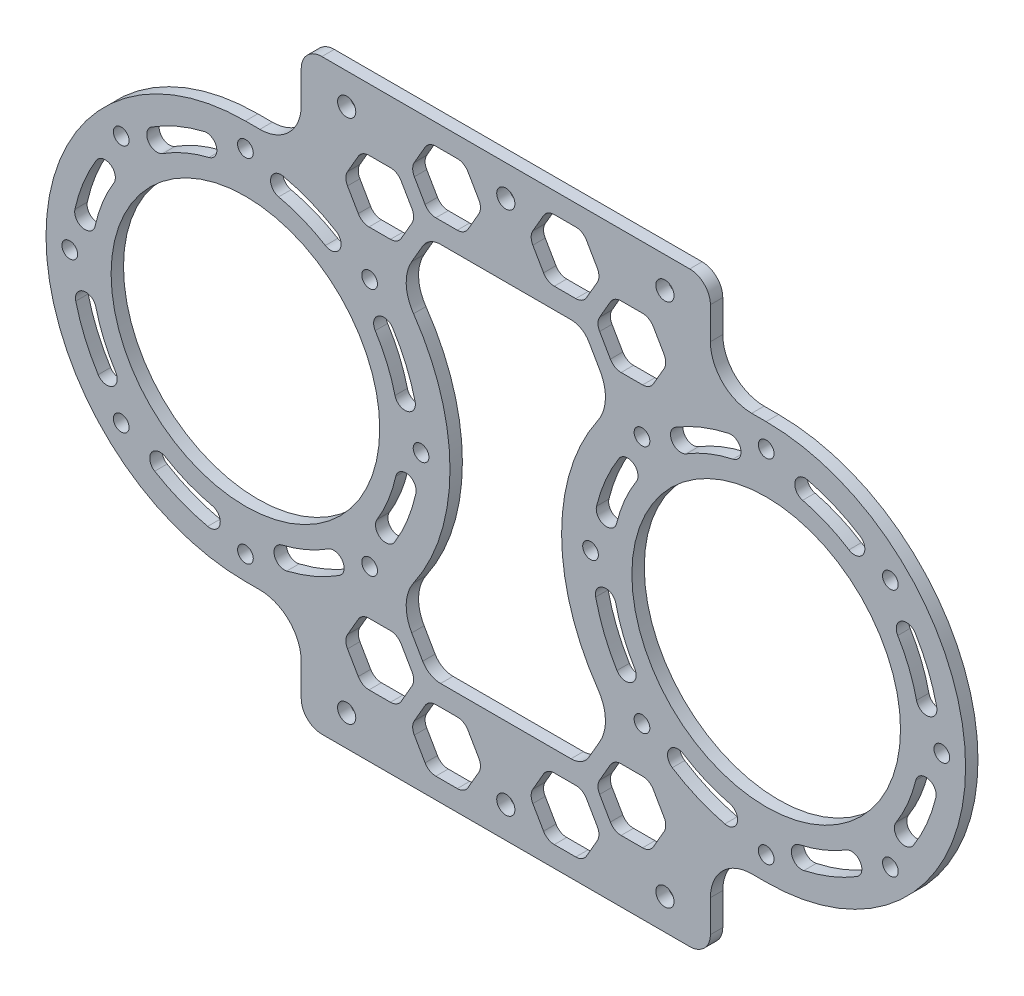
SolidWorks part; units mm, degrees
ref_plane "前视基准面" through (0, 0, 0) normal (0, 0, 1) x (1, 0, 0)
ref_plane "上视基准面" through (0, 0, 0) normal (0, 1, 0) x (1, 0, 0)
ref_plane "右视基准面" through (0, 0, 0) normal (1, 0, 0) x (0, 0, -1)
other "Configuration Table"
sketch "草图1" plane through (0, 0, 0) normal (0, 0, 1) x (1, 0, 0)
  line L0 (0, 0) -> (126, 0) construction
  line L1 (0, 48.25) -> (126, 48.25)
  line L2 (0, -48.25) -> (126, -48.25)
  line L3 (63, 48.25) -> (63, -48.25) construction
  arc A0 (0, 48.25) -> (0, -48.25) centre (0, 0) ccw
  arc A1 (126, -48.25) -> (126, 48.25) centre (126, 0) ccw
  circle A2 centre (126, 0) radius 32.5
  circle A3 centre (0, 0) radius 32.5
  circle A4 centre (0, 0) radius 42.5 construction
  circle A5 centre (126, 0) radius 42.5 construction
  circle A6 centre (0, 42.5) radius 1.9
  circle A7 centre (30.052, 30.052) radius 1.9
  circle A8 centre (42.5, 0) radius 1.9
  circle A9 centre (30.052, -30.052) radius 1.9
  circle A10 centre (0, -42.5) radius 1.9
  circle A11 centre (-30.052, -30.052) radius 1.9
  circle A12 centre (-42.5, 0) radius 1.9
  circle A13 centre (-30.052, 30.052) radius 1.9
  circle A14 centre (156.052, 30.052) radius 1.9
  circle A15 centre (83.5, 0) radius 1.9
  circle A16 centre (95.948, -30.052) radius 1.9
  circle A17 centre (126, -42.5) radius 1.9
  circle A18 centre (156.052, -30.052) radius 1.9
  circle A19 centre (168.5, 0) radius 1.9
  circle A20 centre (126, 0) radius 42.5 construction
  circle A21 centre (126, 42.5) radius 1.9
  circle A22 centre (95.948, 30.052) radius 1.9
  point P3 (63, 0)
  point P35 (0, 0)
  dimension "D2" = 48.25
  dimension "D3" = 65
  dimension "D4" = 85
  dimension "D5" = 3.8
  dimension "D1" = 126
  dimension "D7" = 45
  dimension "D6" = 8
extrude "凸台-拉伸1" add sketch "草图1" along normal blind 3
sketch "草图2" plane through (0, 0, 3) normal (0, 0, 1) x (1, 0, 0)
  line L0 (63, 48.25) -> (63, -48.25) construction
  line L1 (13.5, 48.25) -> (112.5, 48.25)
  line L2 (0, -48.25) -> (126, -48.25)
  line L3 (126, 48.25) -> (0, 48.25)
  line L4 (0, -48.25) -> (126, -48.25)
  line L5 (126, 48.25) -> (0, 48.25)
  line L6 (13.5, 48.25) -> (13.5, 76)
  line L7 (13.5, 76) -> (112.5, 76)
  line L8 (112.5, 76) -> (112.5, 48.25)
  line L9 (-48.25, 0) -> (174.25, 0) construction
  line L10 (13.5, -76) -> (112.5, -76)
  line L11 (13.5, -48.25) -> (13.5, -76)
  line L12 (13.5, -48.25) -> (112.5, -48.25)
  line L13 (112.5, -76) -> (112.5, -48.25)
  arc A2 (0, 48.25) -> (0, -48.25) centre (0, 0) ccw
  arc A3 (126, -48.25) -> (126, 48.25) centre (126, 0) ccw
  arc A4 (0, 48.25) -> (0, -48.25) centre (0, 0) ccw
  arc A5 (126, -48.25) -> (126, 48.25) centre (126, 0) ccw
  line M19 (126, 48.25) -> (0, 48.25)
  dimension "D2" = 99
  dimension "D3" = 27.75
  dimension "D1" = 0
extrude "凸台-拉伸2" add sketch "草图2" against normal blind 3 contours L8 L7 L6 L5 M19 | L10 L13 L12 L11 region at (63, 62.125, 3)
sketch "草图3" plane through (0, 0, 3) normal (0, 0, 1) x (1, 0, 0)
  line L0 (13.5, 63.5) -> (112.5, 63.5) construction
  line L1 (13.5, 48.25) -> (13.5, 76) construction
  line L2 (112.5, 76) -> (112.5, 48.25) construction
  line L3 (13.5, 76) -> (112.5, 76) construction
  line L4 (63, 76) -> (63, -76) construction
  line L5 (13.5, -76) -> (112.5, -76) construction
  line L6 (-48.25, 0) -> (174.25, 0) construction
  arc A0 (0, 48.25) -> (0, -48.25) centre (0, 0) ccw construction
  arc A1 (126, -48.25) -> (126, 48.25) centre (126, 0) ccw construction
  circle A2 centre (63, 63.5) radius 2.2
  circle A3 centre (24.5, 63.5) radius 2.2
  circle A4 centre (101.5, 63.5) radius 2.2
  circle A5 centre (101.5, -63.5) radius 2.2
  circle A6 centre (63, -63.5) radius 2.2
  circle A7 centre (24.5, -63.5) radius 2.2
  dimension "D2" = 77
  dimension "D3" = 4.4
  dimension "D1" = 12.5
extrude "切除-拉伸1" cut sketch "草图3" against normal blind 55
sketch "草图5" plane through (0, 0, 3) normal (0, 0, 1) x (1, 0, 0)
  line L0 (-48.25, 0) -> (174.25, 0) construction
  line L2 (37.6962, 42.5) -> (40.2942, 47)
  line L3 (40.2942, 50) -> (37.6962, 54.5)
  line L4 (35.0981, 56) -> (29.9019, 56)
  line L5 (63, 76) -> (63, -76) construction
  line L6 (13.5, -76) -> (112.5, -76)
  line L7 (112.5, -76) -> (112.5, -48.25)
  line L8 (112.5, 48.25) -> (112.5, 76)
  line L9 (112.5, 76) -> (13.5, 76)
  line L10 (13.5, 76) -> (13.5, 48.25)
  line L11 (13.5, -48.25) -> (13.5, -76)
  line L12 (13.5, -76) -> (112.5, -76)
  line L13 (112.5, -76) -> (112.5, -48.25)
  line L14 (112.5, 48.25) -> (112.5, 76)
  line L15 (112.5, 76) -> (13.5, 76)
  line L16 (13.5, 76) -> (13.5, 48.25)
  line L17 (13.5, -48.25) -> (13.5, -76)
  line L18 (27.3038, 54.5) -> (24.7058, 50)
  line L19 (24.7058, 47) -> (27.3038, 42.5)
  line L20 (29.9019, 41) -> (35.0981, 41)
  line L22 (54.4393, 33.5) -> (57.0374, 38)
  line L23 (57.0374, 41) -> (54.4393, 45.5)
  line L24 (51.8412, 47) -> (46.6451, 47)
  line L25 (44.047, 45.5) -> (41.4489, 41)
  line L26 (41.4489, 38) -> (44.047, 33.5)
  line L27 (46.6451, 32) -> (51.8412, 32)
  line L28 (57.9034, 39.5) -> (57.9034, 20.5)
  line L35 (53.862, 52.5) -> (56.46, 57)
  line L36 (56.46, 60) -> (53.862, 64.5)
  line L37 (51.2639, 66) -> (46.0677, 66)
  line L38 (43.4697, 64.5) -> (40.8716, 60)
  line L39 (40.8716, 57) -> (43.4697, 52.5)
  line L40 (46.0677, 51) -> (51.2639, 51)
  line L41 (54.4393, 14.5) -> (57.0374, 19)
  line L42 (57.0374, 22) -> (54.4393, 26.5)
  line L43 (51.8412, 28) -> (46.6451, 28)
  line L44 (44.047, 26.5) -> (41.4489, 22)
  line L45 (41.4489, 19) -> (44.047, 14.5)
  line L46 (46.6451, 13) -> (51.8412, 13)
  line L119 (46.0677, -51) -> (51.2639, -51)
  line L120 (40.8716, -57) -> (43.4697, -52.5)
  line L121 (43.4697, -64.5) -> (40.8716, -60)
  line L122 (51.2639, -66) -> (46.0677, -66)
  line L123 (56.46, -60) -> (53.862, -64.5)
  line L124 (53.862, -52.5) -> (56.46, -57)
  line L125 (46.6451, -13) -> (51.8412, -13)
  line L126 (41.4489, -19) -> (44.047, -14.5)
  line L127 (44.047, -26.5) -> (41.4489, -22)
  line L128 (51.8412, -28) -> (46.6451, -28)
  line L129 (57.0374, -22) -> (54.4393, -26.5)
  line L130 (54.4393, -14.5) -> (57.0374, -19)
  line L131 (46.6451, -32) -> (51.8412, -32)
  line L132 (41.4489, -38) -> (44.047, -33.5)
  line L133 (44.047, -45.5) -> (41.4489, -41)
  line L134 (51.8412, -47) -> (46.6451, -47)
  line L135 (57.0374, -41) -> (54.4393, -45.5)
  line L136 (54.4393, -33.5) -> (57.0374, -38)
  line L137 (29.9019, -41) -> (35.0981, -41)
  line L138 (24.7058, -47) -> (27.3038, -42.5)
  line L139 (27.3038, -54.5) -> (24.7058, -50)
  line L140 (35.0981, -56) -> (29.9019, -56)
  line L141 (40.2942, -50) -> (37.6962, -54.5)
  line L142 (37.6962, -42.5) -> (40.2942, -47)
  line L143 (84.5511, -38) -> (81.953, -33.5)
  line L144 (81.953, -45.5) -> (84.5511, -41)
  line L145 (74.1588, -47) -> (79.3549, -47)
  line L146 (68.9626, -41) -> (71.5607, -45.5)
  line L147 (71.5607, -33.5) -> (68.9626, -38)
  line L148 (79.3549, -32) -> (74.1588, -32)
  line L149 (85.1284, -57) -> (82.5303, -52.5)
  line L150 (82.5303, -64.5) -> (85.1284, -60)
  line L151 (74.7361, -66) -> (79.9323, -66)
  line L152 (69.54, -60) -> (72.138, -64.5)
  line L153 (72.138, -52.5) -> (69.54, -57)
  line L154 (79.9323, -51) -> (74.7361, -51)
  line L155 (101.2942, -47) -> (98.6962, -42.5)
  line L156 (98.6962, -54.5) -> (101.2942, -50)
  line L157 (90.9019, -56) -> (96.0981, -56)
  line L158 (85.7058, -50) -> (88.3038, -54.5)
  line L159 (88.3038, -42.5) -> (85.7058, -47)
  line L160 (96.0981, -41) -> (90.9019, -41)
  line L161 (84.5511, -19) -> (81.953, -14.5)
  line L162 (81.953, -26.5) -> (84.5511, -22)
  line L163 (74.1588, -28) -> (79.3549, -28)
  line L164 (68.9626, -22) -> (71.5607, -26.5)
  line L165 (71.5607, -14.5) -> (68.9626, -19)
  line L166 (79.3549, -13) -> (74.1588, -13)
  line L167 (79.3549, 13) -> (74.1588, 13)
  line L168 (84.5511, 19) -> (81.953, 14.5)
  line L169 (81.953, 26.5) -> (84.5511, 22)
  line L170 (74.1588, 28) -> (79.3549, 28)
  line L171 (68.9626, 22) -> (71.5607, 26.5)
  line L172 (71.5607, 14.5) -> (68.9626, 19)
  line L173 (79.3549, 32) -> (74.1588, 32)
  line L174 (84.5511, 38) -> (81.953, 33.5)
  line L175 (81.953, 45.5) -> (84.5511, 41)
  line L176 (74.1588, 47) -> (79.3549, 47)
  line L177 (68.9626, 41) -> (71.5607, 45.5)
  line L178 (71.5607, 33.5) -> (68.9626, 38)
  line L179 (96.0981, 41) -> (90.9019, 41)
  line L180 (101.2942, 47) -> (98.6962, 42.5)
  line L181 (98.6962, 54.5) -> (101.2942, 50)
  line L182 (90.9019, 56) -> (96.0981, 56)
  line L183 (85.7058, 50) -> (88.3038, 54.5)
  line L184 (88.3038, 42.5) -> (85.7058, 47)
  line L185 (79.9323, 51) -> (74.7361, 51)
  line L186 (85.1284, 57) -> (82.5303, 52.5)
  line L187 (82.5303, 64.5) -> (85.1284, 60)
  line L188 (74.7361, 66) -> (79.9323, 66)
  line L189 (69.54, 60) -> (72.138, 64.5)
  line L190 (72.138, 52.5) -> (69.54, 57)
  line L192 (67.3301, -7.5) -> (71.6603, 0)
  line L193 (71.6603, 0) -> (67.3301, 7.5)
  line L194 (67.3301, 7.5) -> (58.6699, 7.5)
  line L195 (58.6699, 7.5) -> (54.3397, 0)
  line L196 (54.3397, 0) -> (58.6699, -7.5)
  line L197 (58.6699, -7.5) -> (67.3301, -7.5)
  line L207 (112.5, -48.25) -> (126, -48.25)
  line L208 (112.5, -48.25) -> (126, -48.25)
  line L209 (126, 48.25) -> (112.5, 48.25)
  line L210 (126, 48.25) -> (112.5, 48.25)
  line L211 (13.5, 48.25) -> (0, 48.25)
  line L212 (13.5, 48.25) -> (0, 48.25)
  line L213 (0, -48.25) -> (13.5, -48.25)
  line L214 (0, -48.25) -> (13.5, -48.25)
  circle A0 centre (0, 0) radius 32.5 construction
  circle A1 centre (0, 0) radius 32.5
  circle A2 centre (126, 0) radius 32.5 construction
  circle A3 centre (126, 0) radius 32.5
  circle A4 centre (126, 0) radius 51
  circle A5 centre (0, 0) radius 51
  circle A6 centre (32.5, 48.5) radius 7.5 construction
  circle A7 centre (49.2432, 39.5) radius 7.5 construction
  arc A8 (46.6451, 28) -> (44.047, 26.5) centre (46.6451, 25) ccw
  circle A9 centre (48.6658, 58.5) radius 7.5 construction
  arc A12 (126, -48.25) -> (126, 48.25) centre (126, 0) ccw
  arc A17 (0, 48.25) -> (0, -48.25) centre (0, 0) ccw
  arc A22 (126, -48.25) -> (126, 48.25) centre (126, 0) ccw
  arc A27 (0, 48.25) -> (0, -48.25) centre (0, 0) ccw
  circle A30 centre (49.2432, 20.5) radius 7.5 construction
  arc A31 (41.4489, 22) -> (41.4489, 19) centre (44.047, 20.5) ccw
  arc A32 (44.047, 14.5) -> (46.6451, 13) centre (46.6451, 16) ccw
  arc A33 (54.4393, 14.5) -> (51.8412, 13) centre (51.8412, 16) cw
  arc A34 (57.0374, 19) -> (57.0374, 22) centre (54.4393, 20.5) ccw
  arc A35 (54.4393, 26.5) -> (51.8412, 28) centre (51.8412, 25) ccw
  arc A36 (54.4393, 45.5) -> (51.8412, 47) centre (51.8412, 44) ccw
  arc A37 (57.0374, 38) -> (57.0374, 41) centre (54.4393, 39.5) ccw
  arc A38 (54.4393, 33.5) -> (51.8412, 32) centre (51.8412, 35) cw
  arc A39 (44.047, 33.5) -> (46.6451, 32) centre (46.6451, 35) ccw
  arc A40 (41.4489, 41) -> (41.4489, 38) centre (44.047, 39.5) ccw
  arc A41 (44.047, 45.5) -> (46.6451, 47) centre (46.6451, 44) cw
  arc A42 (37.6962, 54.5) -> (35.0981, 56) centre (35.0981, 53) ccw
  arc A43 (40.2942, 50) -> (40.2942, 47) centre (37.6962, 48.5) cw
  arc A44 (37.6962, 42.5) -> (35.0981, 41) centre (35.0981, 44) cw
  arc A45 (29.9019, 41) -> (27.3038, 42.5) centre (29.9019, 44) cw
  arc A46 (24.7058, 50) -> (24.7058, 47) centre (27.3038, 48.5) ccw
  arc A47 (27.3038, 54.5) -> (29.9019, 56) centre (29.9019, 53) cw
  arc A48 (40.8716, 57) -> (40.8716, 60) centre (43.4697, 58.5) cw
  arc A49 (46.0677, 51) -> (43.4697, 52.5) centre (46.0677, 54) cw
  arc A50 (53.862, 52.5) -> (51.2639, 51) centre (51.2639, 54) cw
  arc A51 (56.46, 57) -> (56.46, 60) centre (53.862, 58.5) ccw
  arc A52 (53.862, 64.5) -> (51.2639, 66) centre (51.2639, 63) ccw
  arc A53 (43.4697, 64.5) -> (46.0677, 66) centre (46.0677, 63) cw
  arc A54 (46.0677, -51) -> (43.4697, -52.5) centre (46.0677, -54) ccw
  arc A55 (40.8716, -57) -> (40.8716, -60) centre (43.4697, -58.5) ccw
  arc A56 (43.4697, -64.5) -> (46.0677, -66) centre (46.0677, -63) ccw
  arc A57 (53.862, -64.5) -> (51.2639, -66) centre (51.2639, -63) cw
  arc A58 (53.862, -52.5) -> (51.2639, -51) centre (51.2639, -54) ccw
  arc A59 (56.46, -57) -> (56.46, -60) centre (53.862, -58.5) cw
  arc A60 (44.047, -14.5) -> (46.6451, -13) centre (46.6451, -16) cw
  arc A61 (41.4489, -22) -> (41.4489, -19) centre (44.047, -20.5) cw
  arc A62 (46.6451, -28) -> (44.047, -26.5) centre (46.6451, -25) cw
  arc A63 (54.4393, -26.5) -> (51.8412, -28) centre (51.8412, -25) cw
  arc A64 (54.4393, -14.5) -> (51.8412, -13) centre (51.8412, -16) ccw
  arc A65 (57.0374, -19) -> (57.0374, -22) centre (54.4393, -20.5) cw
  arc A66 (44.047, -33.5) -> (46.6451, -32) centre (46.6451, -35) cw
  arc A67 (41.4489, -41) -> (41.4489, -38) centre (44.047, -39.5) cw
  arc A68 (44.047, -45.5) -> (46.6451, -47) centre (46.6451, -44) ccw
  arc A69 (54.4393, -45.5) -> (51.8412, -47) centre (51.8412, -44) cw
  arc A70 (57.0374, -38) -> (57.0374, -41) centre (54.4393, -39.5) cw
  arc A71 (54.4393, -33.5) -> (51.8412, -32) centre (51.8412, -35) ccw
  arc A72 (29.9019, -41) -> (27.3038, -42.5) centre (29.9019, -44) ccw
  arc A73 (24.7058, -50) -> (24.7058, -47) centre (27.3038, -48.5) cw
  arc A74 (27.3038, -54.5) -> (29.9019, -56) centre (29.9019, -53) ccw
  arc A75 (37.6962, -54.5) -> (35.0981, -56) centre (35.0981, -53) cw
  arc A76 (40.2942, -50) -> (40.2942, -47) centre (37.6962, -48.5) ccw
  arc A77 (37.6962, -42.5) -> (35.0981, -41) centre (35.0981, -44) ccw
  arc A78 (81.953, -33.5) -> (79.3549, -32) centre (79.3549, -35) ccw
  arc A79 (84.5511, -41) -> (84.5511, -38) centre (81.953, -39.5) ccw
  arc A80 (81.953, -45.5) -> (79.3549, -47) centre (79.3549, -44) cw
  arc A81 (71.5607, -45.5) -> (74.1588, -47) centre (74.1588, -44) ccw
  arc A82 (68.9626, -38) -> (68.9626, -41) centre (71.5607, -39.5) ccw
  arc A83 (71.5607, -33.5) -> (74.1588, -32) centre (74.1588, -35) cw
  arc A84 (79.9323, -51) -> (82.5303, -52.5) centre (79.9323, -54) cw
  arc A85 (85.1284, -57) -> (85.1284, -60) centre (82.5303, -58.5) cw
  arc A86 (82.5303, -64.5) -> (79.9323, -66) centre (79.9323, -63) cw
  arc A87 (72.138, -64.5) -> (74.7361, -66) centre (74.7361, -63) ccw
  arc A88 (69.54, -57) -> (69.54, -60) centre (72.138, -58.5) ccw
  arc A89 (72.138, -52.5) -> (74.7361, -51) centre (74.7361, -54) cw
  arc A90 (96.0981, -41) -> (98.6962, -42.5) centre (96.0981, -44) cw
  arc A91 (101.2942, -50) -> (101.2942, -47) centre (98.6962, -48.5) ccw
  arc A92 (98.6962, -54.5) -> (96.0981, -56) centre (96.0981, -53) cw
  arc A93 (88.3038, -54.5) -> (90.9019, -56) centre (90.9019, -53) ccw
  arc A94 (85.7058, -50) -> (85.7058, -47) centre (88.3038, -48.5) cw
  arc A95 (88.3038, -42.5) -> (90.9019, -41) centre (90.9019, -44) cw
  arc A96 (81.953, -14.5) -> (79.3549, -13) centre (79.3549, -16) ccw
  arc A97 (84.5511, -22) -> (84.5511, -19) centre (81.953, -20.5) ccw
  arc A98 (79.3549, -28) -> (81.953, -26.5) centre (79.3549, -25) ccw
  arc A99 (71.5607, -26.5) -> (74.1588, -28) centre (74.1588, -25) ccw
  arc A100 (68.9626, -19) -> (68.9626, -22) centre (71.5607, -20.5) ccw
  arc A101 (71.5607, -14.5) -> (74.1588, -13) centre (74.1588, -16) cw
  arc A102 (81.953, 14.5) -> (79.3549, 13) centre (79.3549, 16) cw
  arc A103 (84.5511, 22) -> (84.5511, 19) centre (81.953, 20.5) cw
  arc A104 (79.3549, 28) -> (81.953, 26.5) centre (79.3549, 25) cw
  arc A105 (71.5607, 26.5) -> (74.1588, 28) centre (74.1588, 25) cw
  arc A106 (71.5607, 14.5) -> (74.1588, 13) centre (74.1588, 16) ccw
  arc A107 (68.9626, 19) -> (68.9626, 22) centre (71.5607, 20.5) cw
  arc A108 (81.953, 33.5) -> (79.3549, 32) centre (79.3549, 35) cw
  arc A109 (84.5511, 41) -> (84.5511, 38) centre (81.953, 39.5) cw
  arc A110 (81.953, 45.5) -> (79.3549, 47) centre (79.3549, 44) ccw
  arc A111 (71.5607, 45.5) -> (74.1588, 47) centre (74.1588, 44) cw
  arc A112 (68.9626, 38) -> (68.9626, 41) centre (71.5607, 39.5) cw
  arc A113 (71.5607, 33.5) -> (74.1588, 32) centre (74.1588, 35) ccw
  arc A114 (96.0981, 41) -> (98.6962, 42.5) centre (96.0981, 44) ccw
  arc A115 (101.2942, 50) -> (101.2942, 47) centre (98.6962, 48.5) cw
  arc A116 (98.6962, 54.5) -> (96.0981, 56) centre (96.0981, 53) ccw
  arc A117 (88.3038, 54.5) -> (90.9019, 56) centre (90.9019, 53) cw
  arc A118 (85.7058, 50) -> (85.7058, 47) centre (88.3038, 48.5) ccw
  arc A119 (88.3038, 42.5) -> (90.9019, 41) centre (90.9019, 44) ccw
  arc A120 (79.9323, 51) -> (82.5303, 52.5) centre (79.9323, 54) ccw
  arc A121 (85.1284, 57) -> (85.1284, 60) centre (82.5303, 58.5) ccw
  arc A122 (82.5303, 64.5) -> (79.9323, 66) centre (79.9323, 63) ccw
  arc A123 (72.138, 64.5) -> (74.7361, 66) centre (74.7361, 63) cw
  arc A124 (72.138, 52.5) -> (74.7361, 51) centre (74.7361, 54) ccw
  arc A125 (69.54, 57) -> (69.54, 60) centre (72.138, 58.5) cw
  circle A126 centre (63, 0) radius 7.5 construction
  point P56 (44.913, 28)
  point P60 (40.5829, 20.5)
  point P78 (55.161, 54.75)
  point P81 (42.748, 16.75)
  point P151 (44.913, 13)
  point P154 (53.5733, 13)
  point P160 (53.5733, 28)
  point P163 (53.5733, 47)
  point P169 (53.5733, 32)
  point P172 (44.913, 32)
  point P175 (40.5829, 39.5)
  point P178 (44.913, 47)
  point P181 (36.8301, 56)
  point P184 (41.1603, 48.5)
  point P187 (36.8301, 41)
  point P190 (28.1699, 41)
  point P193 (23.8397, 48.5)
  point P196 (28.1699, 56)
  point P199 (40.0056, 58.5)
  point P202 (44.3357, 51)
  point P205 (52.9959, 51)
  point P208 (57.3261, 58.5)
  point P211 (52.9959, 66)
  point P214 (44.3357, 66)
  point P359 (63, -7.5)
  dimension "D2" = 102
  dimension "D3" = 102
  dimension "D16" = 3
  dimension "D17" = 15
  dimension "D4" = 20
  dimension "D5" = 19
  dimension "D6" = 15
  dimension "D7" = 15
  dimension "D8" = 360
  dimension "D9" = 4
  dimension "D10" = 15
  dimension "D11" = 4
  dimension "D12" = 4
  dimension "D13" = 9
  dimension "D14" = 15
  dimension "D15" = 4
  dimension "D1" = 0
extrude "切除-拉伸2" cut sketch "草图5" against normal blind 43 contours A53 L38 A48 L39 A49 L40 A50 L35 A51 L36 A52 L37 | A47 L18 A46 L19 A5 L20 A44 L2 A43 L3 A42 L4 | A41 L25 A40 L26 A39 L27 A38 L22 A37 L23 A36 L24 | L42 A35 L43 A8 L44 A5 L46 A33 L41 A34 | A107 L172 A106 L167 A4 L169 A104 L170 A105 L171 | L178 A113 L173 A108 L174 A109 L175 A110 L176 A111 L177 A112 | L184 A119 L179 A4 L180 A115 L181 A116 L182 A117 L183 A118 | A125 L190 A124 L185 A120 L186 A121 L187 A122 L188 A123 L189 | A103 L169 A4 L167 A102 L168 | L45 A32 L46 A5 L44 A31 | A61 L127 A5 L125 A60 L126 | A101 L165 A100 L164 A99 L163 A98 L162 A4 L166 | L162 A97 L161 A96 L166 A4 | A65 L130 A64 L125 A5 L127 A62 L128 A63 L129 | L136 A71 L131 A66 L132 A67 L133 A68 L134 A69 L135 A70 | L142 A77 L137 A5 L138 A73 L139 A74 L140 A75 L141 A76 | A59 L124 A58 L119 A54 L120 A55 L121 A56 L122 A57 L123 | A89 L153 A88 L152 A87 L151 A86 L150 A85 L149 A84 L154 | A95 L159 A94 L158 A93 L157 A92 L156 A91 L155 A4 L160 | A83 L147 A82 L146 A81 L145 A80 L144 A79 L143 A78 L148 | A90 L160 A4 L155 | L137 A72 L138 A5 | L179 A114 L180 A4 | A45 L20 A5 L19 | L192 L193 L194 L195 L196 L197 region at (32.5478, 48.5776, 3) region at (28.453, 41.929, 3) region at (44.8846, 18.6285, 3) region at (51.0761, 21.287, 3) region at (44.8846, -18.6285, 3) region at (51.0761, -21.287, 3) region at (32.5478, -48.5776, 3) region at (28.453, -41.929, 3) region at (93.4522, 48.5776, 3) region at (97.547, 41.929, 3) region at (97.547, -41.929, 3) region at (93.4522, -48.5776, 3) region at (74.9239, 21.287, 3) region at (81.1154, 18.6285, 3) region at (81.1154, -18.6285, 3) region at (74.9239, -21.287, 3) region at (49.2432, 39.5, 3) region at (48.6658, 58.5, 3) region at (48.6658, -58.5, 3) region at (49.2432, -39.5, 3) region at (76.7568, -39.5, 3) region at (77.3342, -58.5, 3) region at (76.7568, 39.5, 3) region at (77.3342, 58.5, 3)
sketch "草图7" plane through (0, 0, 3) normal (0, 0, 1) x (1, 0, 0)
  line L0 (13.5, 71) -> (112.5, 71)
  line L1 (0, 0) -> (126, 0) construction
  line L2 (13.5, -71) -> (112.5, -71)
  line L10 (0, -48.25) -> (13.5, -48.25)
  line L11 (13.5, -48.25) -> (13.5, -76)
  line L12 (13.5, -76) -> (112.5, -76)
  line L13 (112.5, -76) -> (112.5, -48.25)
  line L14 (112.5, -48.25) -> (126, -48.25)
  line L15 (126, 48.25) -> (112.5, 48.25)
  line L16 (112.5, 48.25) -> (112.5, 76)
  line L17 (112.5, 76) -> (13.5, 76)
  line L18 (13.5, 76) -> (13.5, 48.25)
  line L19 (13.5, 48.25) -> (0, 48.25)
  line L20 (0, -48.25) -> (13.5, -48.25)
  line L21 (13.5, -48.25) -> (13.5, -76)
  line L22 (13.5, -76) -> (112.5, -76)
  line L23 (112.5, -76) -> (112.5, -48.25)
  line L24 (112.5, -48.25) -> (126, -48.25)
  line L25 (126, 48.25) -> (112.5, 48.25)
  line L26 (112.5, 48.25) -> (112.5, 76)
  line L27 (112.5, 76) -> (13.5, 76)
  line L28 (13.5, 76) -> (13.5, 48.25)
  line L29 (13.5, 48.25) -> (0, 48.25)
  arc A2 (0, 48.25) -> (0, -48.25) centre (0, 0) ccw
  arc A3 (126, -48.25) -> (126, 48.25) centre (126, 0) ccw
  arc A4 (0, 48.25) -> (0, -48.25) centre (0, 0) ccw
  arc A5 (126, -48.25) -> (126, 48.25) centre (126, 0) ccw
  dimension "D2" = 5
  dimension "D1" = 0
extrude "切除-拉伸3" cut sketch "草图7" against normal blind 10 contours L27 L28 L0 L26 | L22 L23 L2 L21 region at (63, 73.5, 3) region at (63, -73.5, 3)
fillet "圆角1" radius 5 4 edges at (13.5, -71, 1.5) (112.5, -71, 1.5) (13.5, 71, 1.5) (112.5, 71, 1.5)
fillet "圆角2" radius 10 4 edges at (112.5, 48.25, 1.5) (13.5, -48.25, 1.5) (112.5, -48.25, 1.5) (13.5, 48.25, 1.5)
sketch "草图8" plane through (0, 0, 3) normal (0, 0, 1) x (1, 0, 0)
  line L0 (0, 42.25) -> (0, -42.25) construction
  line L1 (0, 0) -> (-16.5874, 38.8577) construction
  line L2 (63, 71) -> (63, -71) construction
  line L10 (0, -48.25) -> (3.5, -48.25)
  line L11 (13.5, -58.25) -> (13.5, -66)
  line L12 (18.5, -71) -> (107.5, -71)
  line L13 (112.5, -66) -> (112.5, -58.25)
  line L14 (122.5, -48.25) -> (126, -48.25)
  line L15 (126, 48.25) -> (122.5, 48.25)
  line L16 (112.5, 58.25) -> (112.5, 66)
  line L17 (107.5, 71) -> (18.5, 71)
  line L18 (13.5, 66) -> (13.5, 58.25)
  line L19 (3.5, 48.25) -> (0, 48.25)
  line L20 (0, -48.25) -> (3.5, -48.25)
  line L21 (13.5, -58.25) -> (13.5, -66)
  line L22 (18.5, -71) -> (107.5, -71)
  line L23 (112.5, -66) -> (112.5, -58.25)
  line L24 (122.5, -48.25) -> (126, -48.25)
  line L25 (126, 48.25) -> (122.5, 48.25)
  line L26 (112.5, 58.25) -> (112.5, 66)
  line L27 (107.5, 71) -> (18.5, 71)
  line L28 (13.5, 66) -> (13.5, 58.25)
  line L29 (3.5, 48.25) -> (0, 48.25)
  circle A0 centre (0, 0) radius 42.25
  circle A1 centre (0, 0) radius 37.25
  circle A2 centre (-9.4177, 38.6182) radius 2.5
  circle A3 centre (-21.3739, 33.5144) radius 2.5
  circle A4 centre (8.5846, 38.8119) radius 2.5
  circle A5 centre (20.6479, 33.9666) radius 2.5
  circle A6 centre (33.5144, 21.3739) radius 2.5
  circle A7 centre (38.6182, 9.4177) radius 2.5
  circle A8 centre (38.8119, -8.5846) radius 2.5
  circle A9 centre (33.9666, -20.6479) radius 2.5
  arc A10 (13.5, -58.25) -> (3.5, -48.25) centre (3.5, -58.25) ccw
  arc A11 (13.5, -66) -> (18.5, -71) centre (18.5, -66) ccw
  arc A12 (107.5, -71) -> (112.5, -66) centre (107.5, -66) ccw
  arc A13 (122.5, -48.25) -> (112.5, -58.25) centre (122.5, -58.25) ccw
  arc A14 (126, -48.25) -> (126, 48.25) centre (126, 0) ccw
  arc A15 (112.5, 58.25) -> (122.5, 48.25) centre (122.5, 58.25) ccw
  arc A16 (112.5, 66) -> (107.5, 71) centre (107.5, 66) ccw
  arc A17 (18.5, 71) -> (13.5, 66) centre (18.5, 66) ccw
  arc A18 (3.5, 48.25) -> (13.5, 58.25) centre (3.5, 58.25) ccw
  arc A19 (0, 48.25) -> (0, -48.25) centre (0, 0) ccw
  arc A20 (13.5, -58.25) -> (3.5, -48.25) centre (3.5, -58.25) ccw
  arc A21 (13.5, -66) -> (18.5, -71) centre (18.5, -66) ccw
  arc A22 (107.5, -71) -> (112.5, -66) centre (107.5, -66) ccw
  arc A23 (122.5, -48.25) -> (112.5, -58.25) centre (122.5, -58.25) ccw
  arc A24 (126, -48.25) -> (126, 48.25) centre (126, 0) ccw
  arc A25 (112.5, 58.25) -> (122.5, 48.25) centre (122.5, 58.25) ccw
  arc A26 (112.5, 66) -> (107.5, 71) centre (107.5, 66) ccw
  arc A27 (18.5, 71) -> (13.5, 66) centre (18.5, 66) ccw
  arc A28 (3.5, 48.25) -> (13.5, 58.25) centre (3.5, 58.25) ccw
  arc A29 (0, 48.25) -> (0, -48.25) centre (0, 0) ccw
  circle A30 centre (21.3739, -33.5144) radius 2.5
  circle A31 centre (9.4177, -38.6182) radius 2.5
  circle A32 centre (-8.5846, -38.8119) radius 2.5
  circle A33 centre (-20.6479, -33.9666) radius 2.5
  circle A34 centre (-33.5144, -21.3739) radius 2.5
  circle A35 centre (-38.6182, -9.4177) radius 2.5
  circle A36 centre (-38.8119, 8.5846) radius 2.5
  circle A37 centre (-33.9666, 20.6479) radius 2.5
  circle A38 centre (164.6182, -9.4177) radius 2.5
  circle A39 centre (159.5144, -21.3739) radius 2.5
  circle A40 centre (134.5846, -38.8119) radius 2.5
  circle A41 centre (146.6479, -33.9666) radius 2.5
  circle A42 centre (116.5823, -38.6182) radius 2.5
  circle A43 centre (104.6261, -33.5144) radius 2.5
  circle A44 centre (92.0334, -20.6479) radius 2.5
  circle A45 centre (87.1881, -8.5846) radius 2.5
  circle A46 centre (87.3818, 9.4177) radius 2.5
  circle A47 centre (92.4856, 21.3739) radius 2.5
  circle A48 centre (105.3521, 33.9666) radius 2.5
  circle A49 centre (117.4154, 38.8119) radius 2.5
  circle A50 centre (135.4177, 38.6182) radius 2.5
  circle A51 centre (147.3739, 33.5144) radius 2.5
  circle A52 centre (159.9666, 20.6479) radius 2.5
  circle A53 centre (164.8119, 8.5846) radius 2.5
  circle A54 centre (126, 0) radius 37.25
  circle A55 centre (126, 0) radius 42.25
  point P70 (0, 0)
  dimension "D2" = 6
  dimension "D3" = 5
  dimension "D4" = 23.116
  dimension "D5" = 13
  dimension "D1" = 0
  dimension "D6" = 8
extrude "切除-拉伸4" cut sketch "草图8" against normal blind 10 contours A3 A1 A2 A0 | A2 | A3 | A4 | A5 A0 A4 A1 | A5 | A6 | A7 A0 A6 A1 | A7 | A8 | A9 A0 A8 A1 | A9 | A31 | A31 A0 A30 A1 | A30 | A33 | A33 A0 A32 A1 | A32 | A34 | A35 | A35 A0 A34 A1 | A36 | A37 A0 A36 A1 | A37 | A48 | A55 A48 A54 A49 | A49 | A50 | A55 A50 A54 A51 | A51 | A52 | A55 A52 A54 A53 | A53 | A55 A38 A54 A39 | A38 | A39 | A55 A41 A54 A40 | A41 | A40 | A55 A42 A54 A43 | A43 | A42 | A55 A44 A54 A45 | A45 | A44 | A55 A46 A54 A47 | A47 | A46 region at (36.5353, 15.596, 3) region at (38.6182, 9.4177, 3) region at (36.8624, -14.8063, 3) region at (38.8119, -8.5846, 3) region at (33.5144, 21.3739, 3) region at (33.9666, -20.6479, 3) region at (14.8063, 36.8624, 3) region at (20.6479, 33.9666, 3) region at (15.596, -36.5353, 3) region at (21.3739, -33.5144, 3) region at (8.5846, 38.8119, 3) region at (9.4177, -38.6182, 3) region at (-15.596, 36.5353, 3) region at (-9.4177, 38.6182, 3) region at (-14.8063, -36.8624, 3) region at (-8.5846, -38.8119, 3) region at (-21.3739, 33.5144, 3) region at (-20.6479, -33.9666, 3) region at (-36.8624, 14.8063, 3) region at (-33.9666, 20.6479, 3) region at (-36.5353, -15.596, 3) region at (-33.5144, -21.3739, 3) region at (-38.8119, 8.5846, 3) region at (-38.6182, -9.4177, 3) region at (164.6182, -9.4177, 3) region at (162.5353, -15.596, 3) region at (159.5144, -21.3739, 3) region at (146.6479, -33.9666, 3) region at (140.8063, -36.8624, 3) region at (162.8624, 14.8063, 3) region at (164.8119, 8.5846, 3) region at (134.5846, -38.8119, 3) region at (159.9666, 20.6479, 3) region at (116.5823, -38.6182, 3) region at (110.404, -36.5353, 3) region at (141.596, 36.5353, 3) region at (147.3739, 33.5144, 3) region at (104.6261, -33.5144, 3) region at (135.4177, 38.6182, 3) region at (92.0334, -20.6479, 3) region at (89.1376, -14.8063, 3) region at (111.1937, 36.8624, 3) region at (117.4154, 38.8119, 3) region at (87.1881, -8.5846, 3) region at (105.3521, 33.9666, 3) region at (87.3818, 9.4177, 3) region at (89.4647, 15.596, 3) region at (92.4856, 21.3739, 3)
sketch "草图10" plane through (0, 0, 3) normal (0, 0, 1) x (1, 0, 0)
  line L0 (54.4393, -33.5) -> (57.0374, -38) construction
  line L1 (57.0374, -41) -> (54.4393, -45.5) construction
  line L2 (51.8412, -47) -> (46.6451, -47) construction
  line L3 (44.047, -45.5) -> (41.4489, -41) construction
  line L4 (41.4489, -38) -> (44.047, -33.5) construction
  line L5 (46.6451, -32) -> (51.8412, -32) construction
  line L6 (71.5607, -33.5) -> (68.9626, -38) construction
  line L7 (68.9626, -41) -> (71.5607, -45.5) construction
  line L8 (74.1588, -47) -> (79.3549, -47) construction
  line L9 (81.953, -45.5) -> (84.5511, -41) construction
  line L10 (84.5511, -38) -> (81.953, -33.5) construction
  line L11 (79.3549, -32) -> (74.1588, -32) construction
  line L12 (84.5511, -19) -> (81.953, -14.5) construction
  line L13 (71.5607, -14.5) -> (68.9626, -19) construction
  line L14 (79.3549, -13) -> (74.1588, -13) construction
  line L15 (81.953, -26.5) -> (84.5511, -22) construction
  line L16 (74.1588, -28) -> (79.3549, -28) construction
  line L17 (68.9626, -22) -> (71.5607, -26.5) construction
  line L18 (46.6451, -13) -> (51.8412, -13) construction
  line L19 (44.047, -26.5) -> (41.4489, -22) construction
  line L20 (41.4489, -19) -> (44.047, -14.5) construction
  line L21 (54.4393, -14.5) -> (57.0374, -19) construction
  line L22 (57.0374, -22) -> (54.4393, -26.5) construction
  line L23 (51.8412, -28) -> (46.6451, -28) construction
  line L24 (81.953, 26.5) -> (84.5511, 22) construction
  line L25 (84.5511, 19) -> (81.953, 14.5) construction
  line L26 (79.3549, 13) -> (74.1588, 13) construction
  line L27 (71.5607, 14.5) -> (68.9626, 19) construction
  line L28 (68.9626, 22) -> (71.5607, 26.5) construction
  line L29 (74.1588, 28) -> (79.3549, 28) construction
  line L30 (54.4393, 14.5) -> (57.0374, 19) construction
  line L31 (46.6451, 13) -> (51.8412, 13) construction
  line L32 (41.4489, 19) -> (44.047, 14.5) construction
  line L33 (44.047, 26.5) -> (41.4489, 22) construction
  line L34 (51.8412, 28) -> (46.6451, 28) construction
  line L35 (57.0374, 22) -> (54.4393, 26.5) construction
  line L36 (71.6603, 0) -> (67.3301, 7.5) construction
  line L37 (67.3301, -7.5) -> (71.6603, 0) construction
  line L38 (58.6699, -7.5) -> (67.3301, -7.5) construction
  line L39 (54.3397, 0) -> (58.6699, -7.5) construction
  line L40 (58.6699, 7.5) -> (54.3397, 0) construction
  line L41 (67.3301, 7.5) -> (58.6699, 7.5) construction
  line L42 (81.953, 45.5) -> (84.5511, 41) construction
  line L43 (84.5511, 38) -> (81.953, 33.5) construction
  line L44 (79.3549, 32) -> (74.1588, 32) construction
  line L45 (71.5607, 33.5) -> (68.9626, 38) construction
  line L46 (68.9626, 41) -> (71.5607, 45.5) construction
  line L47 (74.1588, 47) -> (79.3549, 47) construction
  line L48 (44.047, 45.5) -> (41.4489, 41) construction
  line L49 (41.4489, 38) -> (44.047, 33.5) construction
  line L50 (46.6451, 32) -> (51.8412, 32) construction
  line L51 (54.4393, 33.5) -> (57.0374, 38) construction
  line L52 (57.0374, 41) -> (54.4393, 45.5) construction
  line L53 (51.8412, 47) -> (46.6451, 47) construction
  line L54 (54.4393, -33.5) -> (57.0374, -38)
  line L55 (57.0374, -41) -> (54.4393, -45.5)
  line L56 (51.8412, -47) -> (46.6451, -47)
  line L57 (44.047, -45.5) -> (41.4489, -41)
  line L58 (41.4489, -38) -> (44.047, -33.5)
  line L59 (46.6451, -32) -> (51.8412, -32)
  line L60 (71.5607, -33.5) -> (68.9626, -38)
  line L61 (68.9626, -41) -> (71.5607, -45.5)
  line L62 (74.1588, -47) -> (79.3549, -47)
  line L63 (81.953, -45.5) -> (84.5511, -41)
  line L64 (84.5511, -38) -> (81.953, -33.5)
  line L65 (79.3549, -32) -> (74.1588, -32)
  line L66 (84.5511, -19) -> (81.953, -14.5)
  line L67 (71.5607, -14.5) -> (68.9626, -19)
  line L68 (79.3549, -13) -> (74.1588, -13)
  line L69 (81.953, -26.5) -> (84.5511, -22)
  line L70 (74.1588, -28) -> (79.3549, -28)
  line L71 (68.9626, -22) -> (71.5607, -26.5)
  line L72 (46.6451, -13) -> (51.8412, -13)
  line L73 (44.047, -26.5) -> (41.4489, -22)
  line L74 (41.4489, -19) -> (44.047, -14.5)
  line L75 (54.4393, -14.5) -> (57.0374, -19)
  line L76 (57.0374, -22) -> (54.4393, -26.5)
  line L77 (51.8412, -28) -> (46.6451, -28)
  line L78 (81.953, 26.5) -> (84.5511, 22)
  line L79 (84.5511, 19) -> (81.953, 14.5)
  line L80 (79.3549, 13) -> (74.1588, 13)
  line L81 (71.5607, 14.5) -> (68.9626, 19)
  line L82 (68.9626, 22) -> (71.5607, 26.5)
  line L83 (74.1588, 28) -> (79.3549, 28)
  line L84 (54.4393, 14.5) -> (57.0374, 19)
  line L85 (46.6451, 13) -> (51.8412, 13)
  line L86 (41.4489, 19) -> (44.047, 14.5)
  line L87 (44.047, 26.5) -> (41.4489, 22)
  line L88 (51.8412, 28) -> (46.6451, 28)
  line L89 (57.0374, 22) -> (54.4393, 26.5)
  line L90 (71.6603, 0) -> (67.3301, 7.5)
  line L91 (67.3301, -7.5) -> (71.6603, 0)
  line L92 (58.6699, -7.5) -> (67.3301, -7.5)
  line L93 (54.3397, 0) -> (58.6699, -7.5)
  line L94 (58.6699, 7.5) -> (54.3397, 0)
  line L95 (67.3301, 7.5) -> (58.6699, 7.5)
  line L96 (81.953, 45.5) -> (84.5511, 41)
  line L97 (84.5511, 38) -> (81.953, 33.5)
  line L98 (79.3549, 32) -> (74.1588, 32)
  line L99 (71.5607, 33.5) -> (68.9626, 38)
  line L100 (68.9626, 41) -> (71.5607, 45.5)
  line L101 (74.1588, 47) -> (79.3549, 47)
  line L102 (44.047, 45.5) -> (41.4489, 41)
  line L103 (41.4489, 38) -> (44.047, 33.5)
  line L104 (46.6451, 32) -> (51.8412, 32)
  line L105 (54.4393, 33.5) -> (57.0374, 38)
  line L106 (57.0374, 41) -> (54.4393, 45.5)
  line L107 (51.8412, 47) -> (46.6451, 47)
  line L118 (0, -48.25) -> (3.5, -48.25)
  line L119 (13.5, -58.25) -> (13.5, -66)
  line L120 (18.5, -71) -> (107.5, -71)
  line L121 (112.5, -66) -> (112.5, -58.25)
  line L122 (122.5, -48.25) -> (126, -48.25)
  line L123 (126, 48.25) -> (122.5, 48.25)
  line L124 (112.5, 58.25) -> (112.5, 66)
  line L125 (107.5, 71) -> (18.5, 71)
  line L126 (13.5, 66) -> (13.5, 58.25)
  line L127 (3.5, 48.25) -> (0, 48.25)
  line L128 (0, -48.25) -> (3.5, -48.25)
  line L129 (13.5, -58.25) -> (13.5, -66)
  line L130 (18.5, -71) -> (107.5, -71)
  line L131 (112.5, -66) -> (112.5, -58.25)
  line L132 (122.5, -48.25) -> (126, -48.25)
  line L133 (126, 48.25) -> (122.5, 48.25)
  line L134 (112.5, 58.25) -> (112.5, 66)
  line L135 (107.5, 71) -> (18.5, 71)
  line L136 (13.5, 66) -> (13.5, 58.25)
  line L137 (3.5, 48.25) -> (0, 48.25)
  arc A0 (57.0374, -41) -> (57.0374, -38) centre (54.4393, -39.5) ccw construction
  arc A1 (51.8412, -47) -> (54.4393, -45.5) centre (51.8412, -44) ccw construction
  arc A2 (44.047, -45.5) -> (46.6451, -47) centre (46.6451, -44) ccw construction
  arc A3 (41.4489, -38) -> (41.4489, -41) centre (44.047, -39.5) ccw construction
  arc A4 (46.6451, -32) -> (44.047, -33.5) centre (46.6451, -35) ccw construction
  arc A5 (54.4393, -33.5) -> (51.8412, -32) centre (51.8412, -35) ccw construction
  arc A6 (74.1588, -32) -> (71.5607, -33.5) centre (74.1588, -35) ccw construction
  arc A7 (68.9626, -38) -> (68.9626, -41) centre (71.5607, -39.5) ccw construction
  arc A8 (71.5607, -45.5) -> (74.1588, -47) centre (74.1588, -44) ccw construction
  arc A9 (79.3549, -47) -> (81.953, -45.5) centre (79.3549, -44) ccw construction
  arc A10 (84.5511, -41) -> (84.5511, -38) centre (81.953, -39.5) ccw construction
  arc A11 (81.953, -33.5) -> (79.3549, -32) centre (79.3549, -35) ccw construction
  arc A12 (79.3549, -28) -> (81.953, -26.5) centre (79.3549, -25) ccw construction
  arc A13 (71.5607, -26.5) -> (74.1588, -28) centre (74.1588, -25) ccw construction
  arc A14 (68.9626, -19) -> (68.9626, -22) centre (71.5607, -20.5) ccw construction
  arc A15 (84.5511, -22) -> (84.5511, -19) centre (81.953, -20.5) ccw construction
  arc A16 (74.1588, -13) -> (71.5607, -14.5) centre (74.1588, -16) ccw construction
  arc A17 (81.953, -14.5) -> (79.3549, -13) centre (79.3549, -16) ccw construction
  arc A18 (44.047, -26.5) -> (46.6451, -28) centre (46.6451, -25) ccw construction
  arc A19 (51.8412, -28) -> (54.4393, -26.5) centre (51.8412, -25) ccw construction
  arc A20 (57.0374, -22) -> (57.0374, -19) centre (54.4393, -20.5) ccw construction
  arc A21 (46.6451, -13) -> (44.047, -14.5) centre (46.6451, -16) ccw construction
  arc A22 (54.4393, -14.5) -> (51.8412, -13) centre (51.8412, -16) ccw construction
  arc A23 (41.4489, -19) -> (41.4489, -22) centre (44.047, -20.5) ccw construction
  arc A24 (84.5511, 19) -> (84.5511, 22) centre (81.953, 20.5) ccw construction
  arc A25 (79.3549, 13) -> (81.953, 14.5) centre (79.3549, 16) ccw construction
  arc A26 (71.5607, 14.5) -> (74.1588, 13) centre (74.1588, 16) ccw construction
  arc A27 (68.9626, 22) -> (68.9626, 19) centre (71.5607, 20.5) ccw construction
  arc A28 (74.1588, 28) -> (71.5607, 26.5) centre (74.1588, 25) ccw construction
  arc A29 (81.953, 26.5) -> (79.3549, 28) centre (79.3549, 25) ccw construction
  arc A30 (57.0374, 19) -> (57.0374, 22) centre (54.4393, 20.5) ccw construction
  arc A31 (51.8412, 13) -> (54.4393, 14.5) centre (51.8412, 16) ccw construction
  arc A32 (44.047, 14.5) -> (46.6451, 13) centre (46.6451, 16) ccw construction
  arc A33 (41.4489, 22) -> (41.4489, 19) centre (44.047, 20.5) ccw construction
  arc A34 (46.6451, 28) -> (44.047, 26.5) centre (46.6451, 25) ccw construction
  arc A35 (54.4393, 26.5) -> (51.8412, 28) centre (51.8412, 25) ccw construction
  arc A36 (81.953, 45.5) -> (79.3549, 47) centre (79.3549, 44) ccw construction
  arc A37 (84.5511, 38) -> (84.5511, 41) centre (81.953, 39.5) ccw construction
  arc A38 (79.3549, 32) -> (81.953, 33.5) centre (79.3549, 35) ccw construction
  arc A39 (71.5607, 33.5) -> (74.1588, 32) centre (74.1588, 35) ccw construction
  arc A40 (68.9626, 41) -> (68.9626, 38) centre (71.5607, 39.5) ccw construction
  arc A41 (74.1588, 47) -> (71.5607, 45.5) centre (74.1588, 44) ccw construction
  arc A42 (46.6451, 47) -> (44.047, 45.5) centre (46.6451, 44) ccw construction
  arc A43 (41.4489, 41) -> (41.4489, 38) centre (44.047, 39.5) ccw construction
  arc A44 (44.047, 33.5) -> (46.6451, 32) centre (46.6451, 35) ccw construction
  arc A45 (51.8412, 32) -> (54.4393, 33.5) centre (51.8412, 35) ccw construction
  arc A46 (57.0374, 38) -> (57.0374, 41) centre (54.4393, 39.5) ccw construction
  arc A47 (54.4393, 45.5) -> (51.8412, 47) centre (51.8412, 44) ccw construction
  arc A48 (57.0374, -41) -> (57.0374, -38) centre (54.4393, -39.5) ccw
  arc A49 (51.8412, -47) -> (54.4393, -45.5) centre (51.8412, -44) ccw
  arc A50 (44.047, -45.5) -> (46.6451, -47) centre (46.6451, -44) ccw
  arc A51 (41.4489, -38) -> (41.4489, -41) centre (44.047, -39.5) ccw
  arc A52 (46.6451, -32) -> (44.047, -33.5) centre (46.6451, -35) ccw
  arc A53 (54.4393, -33.5) -> (51.8412, -32) centre (51.8412, -35) ccw
  arc A54 (74.1588, -32) -> (71.5607, -33.5) centre (74.1588, -35) ccw
  arc A55 (68.9626, -38) -> (68.9626, -41) centre (71.5607, -39.5) ccw
  arc A56 (71.5607, -45.5) -> (74.1588, -47) centre (74.1588, -44) ccw
  arc A57 (79.3549, -47) -> (81.953, -45.5) centre (79.3549, -44) ccw
  arc A58 (84.5511, -41) -> (84.5511, -38) centre (81.953, -39.5) ccw
  arc A59 (81.953, -33.5) -> (79.3549, -32) centre (79.3549, -35) ccw
  arc A60 (79.3549, -28) -> (81.953, -26.5) centre (79.3549, -25) ccw
  arc A61 (71.5607, -26.5) -> (74.1588, -28) centre (74.1588, -25) ccw
  arc A62 (68.9626, -19) -> (68.9626, -22) centre (71.5607, -20.5) ccw
  arc A63 (84.5511, -22) -> (84.5511, -19) centre (81.953, -20.5) ccw
  arc A64 (74.1588, -13) -> (71.5607, -14.5) centre (74.1588, -16) ccw
  arc A65 (81.953, -14.5) -> (79.3549, -13) centre (79.3549, -16) ccw
  arc A66 (44.047, -26.5) -> (46.6451, -28) centre (46.6451, -25) ccw
  arc A67 (51.8412, -28) -> (54.4393, -26.5) centre (51.8412, -25) ccw
  arc A68 (57.0374, -22) -> (57.0374, -19) centre (54.4393, -20.5) ccw
  arc A69 (46.6451, -13) -> (44.047, -14.5) centre (46.6451, -16) ccw
  arc A70 (54.4393, -14.5) -> (51.8412, -13) centre (51.8412, -16) ccw
  arc A71 (41.4489, -19) -> (41.4489, -22) centre (44.047, -20.5) ccw
  arc A72 (84.5511, 19) -> (84.5511, 22) centre (81.953, 20.5) ccw
  arc A73 (79.3549, 13) -> (81.953, 14.5) centre (79.3549, 16) ccw
  arc A74 (71.5607, 14.5) -> (74.1588, 13) centre (74.1588, 16) ccw
  arc A75 (68.9626, 22) -> (68.9626, 19) centre (71.5607, 20.5) ccw
  arc A76 (74.1588, 28) -> (71.5607, 26.5) centre (74.1588, 25) ccw
  arc A77 (81.953, 26.5) -> (79.3549, 28) centre (79.3549, 25) ccw
  arc A78 (57.0374, 19) -> (57.0374, 22) centre (54.4393, 20.5) ccw
  arc A79 (51.8412, 13) -> (54.4393, 14.5) centre (51.8412, 16) ccw
  arc A80 (44.047, 14.5) -> (46.6451, 13) centre (46.6451, 16) ccw
  arc A81 (41.4489, 22) -> (41.4489, 19) centre (44.047, 20.5) ccw
  arc A82 (46.6451, 28) -> (44.047, 26.5) centre (46.6451, 25) ccw
  arc A83 (54.4393, 26.5) -> (51.8412, 28) centre (51.8412, 25) ccw
  arc A84 (81.953, 45.5) -> (79.3549, 47) centre (79.3549, 44) ccw
  arc A85 (84.5511, 38) -> (84.5511, 41) centre (81.953, 39.5) ccw
  arc A86 (79.3549, 32) -> (81.953, 33.5) centre (79.3549, 35) ccw
  arc A87 (71.5607, 33.5) -> (74.1588, 32) centre (74.1588, 35) ccw
  arc A88 (68.9626, 41) -> (68.9626, 38) centre (71.5607, 39.5) ccw
  arc A89 (74.1588, 47) -> (71.5607, 45.5) centre (74.1588, 44) ccw
  arc A90 (46.6451, 47) -> (44.047, 45.5) centre (46.6451, 44) ccw
  arc A91 (41.4489, 41) -> (41.4489, 38) centre (44.047, 39.5) ccw
  arc A92 (44.047, 33.5) -> (46.6451, 32) centre (46.6451, 35) ccw
  arc A93 (51.8412, 32) -> (54.4393, 33.5) centre (51.8412, 35) ccw
  arc A94 (57.0374, 38) -> (57.0374, 41) centre (54.4393, 39.5) ccw
  arc A95 (54.4393, 45.5) -> (51.8412, 47) centre (51.8412, 44) ccw
  arc A106 (13.5, -58.25) -> (3.5, -48.25) centre (3.5, -58.25) ccw
  arc A107 (13.5, -66) -> (18.5, -71) centre (18.5, -66) ccw
  arc A108 (107.5, -71) -> (112.5, -66) centre (107.5, -66) ccw
  arc A109 (122.5, -48.25) -> (112.5, -58.25) centre (122.5, -58.25) ccw
  arc A110 (126, -48.25) -> (126, 48.25) centre (126, 0) ccw
  arc A111 (112.5, 58.25) -> (122.5, 48.25) centre (122.5, 58.25) ccw
  arc A112 (112.5, 66) -> (107.5, 71) centre (107.5, 66) ccw
  arc A113 (18.5, 71) -> (13.5, 66) centre (18.5, 66) ccw
  arc A114 (3.5, 48.25) -> (13.5, 58.25) centre (3.5, 58.25) ccw
  arc A115 (0, 48.25) -> (0, -48.25) centre (0, 0) ccw
  arc A116 (13.5, -58.25) -> (3.5, -48.25) centre (3.5, -58.25) ccw
  arc A117 (13.5, -66) -> (18.5, -71) centre (18.5, -66) ccw
  arc A118 (107.5, -71) -> (112.5, -66) centre (107.5, -66) ccw
  arc A119 (122.5, -48.25) -> (112.5, -58.25) centre (122.5, -58.25) ccw
  arc A120 (126, -48.25) -> (126, 48.25) centre (126, 0) ccw
  arc A121 (112.5, 58.25) -> (122.5, 48.25) centre (122.5, 58.25) ccw
  arc A122 (112.5, 66) -> (107.5, 71) centre (107.5, 66) ccw
  arc A123 (18.5, 71) -> (13.5, 66) centre (18.5, 66) ccw
  arc A124 (3.5, 48.25) -> (13.5, 58.25) centre (3.5, 58.25) ccw
  arc A125 (0, 48.25) -> (0, -48.25) centre (0, 0) ccw
  dimension "D1" = 0
extrude "凸台-拉伸3" add sketch "草图10" against normal blind 3 contours A90 L102 A91 L103 A92 L104 A93 L105 A94 L106 A95 L107 | A78 L89 A83 L88 A82 L87 A81 L86 A80 L85 A79 L84 | A72 L78 A77 L83 A76 L82 A75 L81 A74 L80 A73 L79 | A84 L101 A89 L100 A88 L99 A87 L98 A86 L97 A85 L96 | L90 L95 L94 L93 L92 L91 | A66 L77 A67 L76 A68 L75 A70 L72 A69 L74 A71 L73 | A60 L69 A63 L66 A65 L68 A64 L67 A62 L71 A61 L70 | A54 L60 A55 L61 A56 L62 A57 L63 A58 L64 A59 L65 | A48 L54 A53 L59 A52 L58 A51 L57 A50 L56 A49 L55
sketch "草图11" plane through (0, 0, 3) normal (0, 0, 1) x (1, 0, 0)
  line L0 (63, 71) -> (63, -71) construction
  line L1 (18.5, 71) -> (107.5, 71) construction
  line L2 (18.5, -71) -> (107.5, -71) construction
  line L3 (44.3357, 46) -> (81.6643, 46)
  line L4 (81.6643, 46) -> (89.1444, 33.0441)
  line L5 (0, 0) -> (126, 0) construction
  line L6 (46.0677, 51) -> (51.2639, 51) construction
  line L7 (44.3357, 46) -> (36.8556, 33.0441)
  line L8 (37.6962, 42.5) -> (40.2942, 47) construction
  line L9 (88.3038, 42.5) -> (85.7058, 47) construction
  line L10 (81.6643, -46) -> (89.1444, -33.0441)
  line L11 (44.3357, -46) -> (81.6643, -46)
  line L12 (44.3357, -46) -> (36.8556, -33.0441)
  circle A0 centre (0, 0) radius 49.5
  circle A1 centre (126, 0) radius 49.5
  dimension "D2" = 99
  dimension "D3" = 4
  dimension "D1" = 5
extrude "切除-拉伸5" cut sketch "草图11" against normal blind 43 contours L10 A1 L4 L3 L7 A0 L12 L11 region at (63, 0, 3)
fillet "圆角3" radius 5 4 edges at (44.3357, -46, 1.5) (81.6643, -46, 1.5) (44.3357, 46, 1.5) (81.6643, 46, 1.5)
fillet "圆角4" radius 10 4 edges at (36.8556, -33.0441, 1.5) (89.1444, -33.0441, 1.5) (89.1444, 33.0441, 1.5) (36.8556, 33.0441, 1.5)
